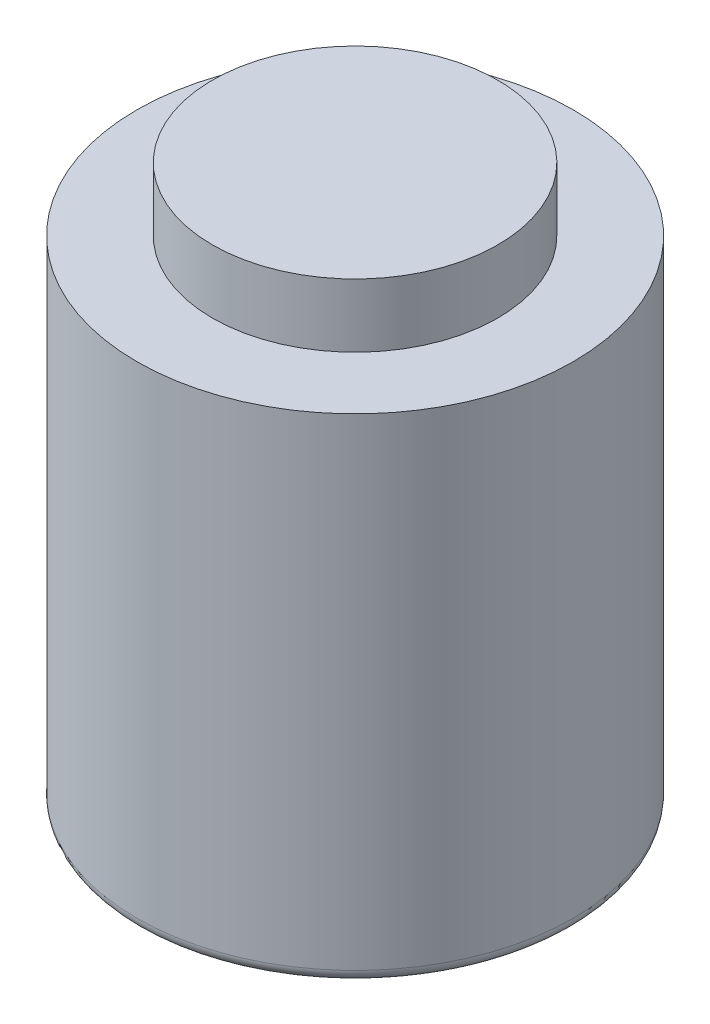
SolidWorks part; units mm, degrees
ref_plane "Plano frontal" through (0, 0, 0) normal (0, 0, 1) x (1, 0, 0)
ref_plane "Plano superior" through (0, 0, 0) normal (0, 1, 0) x (1, 0, 0)
ref_plane "Plano direito" through (0, 0, 0) normal (1, 0, 0) x (0, 0, -1)
sketch "Esboço1" plane through (0, 0, 0) normal (0, 1, 0) x (1, 0, 0)
  circle A0 centre (0, 0) radius 17.2
  dimension "D1" = 34.4
extrude "Ressalto-extrusão1" add sketch "Esboço1" along normal blind 39
sketch "Esboço2" plane through (0, 39, 0) normal (0, 1, 0) x (1, 0, 0)
  circle A0 centre (0, 0) radius 11.25
  dimension "D1" = 22.5
extrude "Ressalto-extrusão2" add sketch "Esboço2" along normal blind 5
sketch "Esboço3" plane through (0, 0, 0) normal (0, -1, 0) x (1, 0, 0)
  circle A0 centre (0, 0) radius 4
  dimension "D1" = 8
extrude "Ressalto-extrusão3" add sketch "Esboço3" along normal blind 3
sketch "Esboço5" plane through (0, -3, 0) normal (0, -1, 0) x (1, 0, 0)
  circle A0 centre (0, 0) radius 1
  dimension "D1" = 2
extrude "Ressalto-extrusão4" add sketch "Esboço5" along normal blind 7
sketch "Esboço6" plane through (0, 0, 0) normal (0, -1, 0) x (1, 0, 0)
  circle A0 centre (0, 0) radius 13.5 construction
  point P3 (0, 13.5)
  dimension "D1" = 27
hole_wizard "Furo roscado de M2.51" positions "3DSketch1" profile "Esboço7" tap size "M2.5" standard "ISO"
sketch3d "3DSketch1"
  point P0 (0, 0, 13.5)
sketch "Esboço7" plane through (0, 0, 13.5) normal (1, 0, 0) x (0, 0, -1)
  line L0 (0, 0) -> (0, 6)
  line L1 (0, 6) -> (1.025, 5.3841)
  line L2 (1.025, 5.3841) -> (1.025, 0)
  line L5 (1.025, 0) -> (0, 0)
  line L10 (0, 6) -> (-1.025, 5.3841) construction
  line L11 (0, -6.35) -> (0, 107.95) construction
  dimension "Tap Drill Dia." = 2.05
  dimension "Tap Drill Depth" = 6
  dimension "Drill Angle" = 118
cosmetic thread "Rosca de furo1" parameters "D1"=5, "D2"=2.5
pattern_circular "PadrãoCircular1" count 6 over 360 about axis through (0, -3, 0) along (0, -1, 0) of "Furo roscado de M2.51"
cosmetic thread "Rosca de furo2" parameters "D1"=5, "D2"=2.5
cosmetic thread "Rosca de furo3" parameters "D1"=5, "D2"=2.5
cosmetic thread "Rosca de furo4" parameters "D1"=5, "D2"=2.5
cosmetic thread "Rosca de furo5" parameters "D1"=5, "D2"=2.5
cosmetic thread "Rosca de furo6" parameters "D1"=5, "D2"=2.5
fillet "Filete1" radius 1 1 edges at (0, 0, 17.2)
